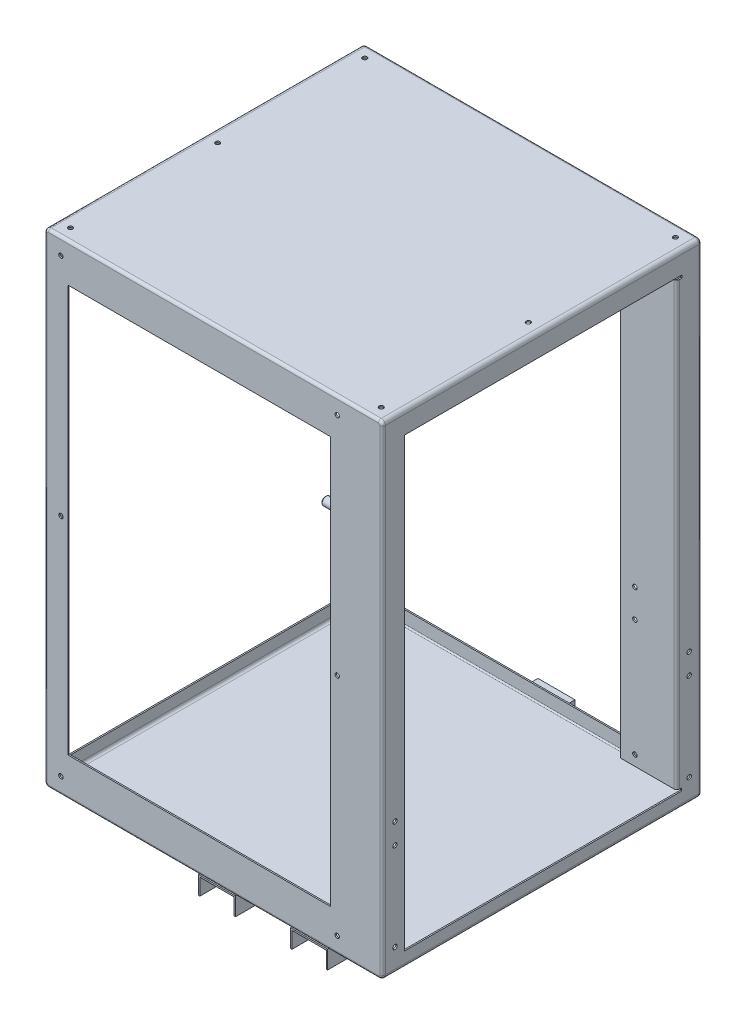
SolidWorks part; units mm, degrees
ref_plane "Спереди" through (0, 0, 0) normal (0, 0, 1) x (1, 0, 0)
ref_plane "Сверху" through (0, 0, 0) normal (0, 1, 0) x (1, 0, 0)
ref_plane "Справа" through (0, 0, 0) normal (1, 0, 0) x (0, 0, -1)
sketch "Эскиз1" plane through (0, 0, 0) normal (0, 0, 1) x (1, 0, 0)
  line L0 (-33.8044, 0) -> (37.3961, 0) construction
  line L1 (0, -31.1634) -> (0, 34.1213) construction
  line L3 (-120, -175) -> (120, -175)
  line L4 (-122, -173) -> (-122, 173)
  line L5 (-120, 175) -> (120, 175)
  line L6 (122, -173) -> (122, 173)
  arc A0 (-122, 173) -> (-120, 175) centre (-120, 173) cw
  arc A1 (120, 175) -> (122, 173) centre (120, 173) cw
  arc A2 (-120, -175) -> (-122, -173) centre (-120, -173) cw
  arc A3 (120, -175) -> (122, -173) centre (120, -173) ccw
  point P11 (-122, 175)
  point P14 (122, 175)
  point P17 (-122, -175)
  dimension "D3" = 2
  dimension "D1" = 350
  dimension "D2" = 244
extrude "Вытянуть-Тонкостенный1" add sketch "Эскиз1" along normal blind 232 thin thin type one direction wall 1
sketch "Эскиз2" plane through (123, 0, 0) normal (1, 0, 0) x (0, 0, -1)
  line L0 (-232, 176) -> (0, 176) construction
  line L1 (-216, -165) -> (-16, -165)
  line L2 (-216, -165) -> (-216, 160)
  line L3 (-216, 160) -> (-16, 160)
  line L4 (-16, -165) -> (-16, 160)
  line L5 (-116, 208.5566) -> (-116, -206.9252) construction
  line L6 (-232, -173) -> (-232, 173) construction
  line L7 (0, -173) -> (0, 173) construction
  dimension "D1" = 200
  dimension "D2" = 325
  dimension "D3" = 16
extrude "Вырез-Вытянуть1" cut sketch "Эскиз2" against normal blind 500
sketch "Эскиз3" plane through (0, 0, 232) normal (0, 0, 1) x (1, 0, 0)
  line L4 (-123, 173) -> (-123, -173)
  line L5 (-120, -176) -> (120, -176)
  line L6 (123, -173) -> (123, 173)
  line L7 (120, 176) -> (-120, 176)
  line L8 (-123, 173) -> (-123, -173)
  line L9 (-120, -176) -> (120, -176)
  line L10 (123, -173) -> (123, 173)
  line L11 (120, 176) -> (-120, 176)
  arc A4 (-120, 176) -> (-123, 173) centre (-120, 173) ccw
  arc A5 (-123, -173) -> (-120, -176) centre (-120, -173) ccw
  arc A6 (120, -176) -> (123, -173) centre (120, -173) ccw
  arc A7 (123, 173) -> (120, 176) centre (120, 173) ccw
  arc A8 (-120, 176) -> (-123, 173) centre (-120, 173) ccw
  arc A9 (-123, -173) -> (-120, -176) centre (-120, -173) ccw
  arc A10 (120, -176) -> (123, -173) centre (120, -173) ccw
  arc A11 (123, 173) -> (120, 176) centre (120, 173) ccw
  dimension "D1" = 0
extrude "Вытянуть1" add sketch "Эскиз3" against normal blind 1
sketch "Эскиз4" plane through (0, 0, 0) normal (0, 0, -1) x (-1, 0, 0)
  line L1 (0, 0) -> (0, 114.475) construction
  line L3 (-107, -165) -> (107, -165)
  line L4 (120, 176) -> (-120, 176)
  line L5 (-123, 173) -> (-123, -173)
  line L6 (-120, -176) -> (120, -176)
  line L7 (123, -173) -> (123, 173)
  line L8 (120, 176) -> (-120, 176)
  line L9 (-123, 173) -> (-123, -173)
  line L10 (-120, -176) -> (120, -176)
  line L11 (123, -173) -> (123, 173)
  line L12 (-107, -165) -> (-107, 160)
  line L13 (-107, 160) -> (107, 160)
  line L14 (107, -165) -> (107, 160)
  arc A4 (123, 173) -> (120, 176) centre (120, 173) ccw
  arc A5 (-120, 176) -> (-123, 173) centre (-120, 173) ccw
  arc A6 (-123, -173) -> (-120, -176) centre (-120, -173) ccw
  arc A7 (120, -176) -> (123, -173) centre (120, -173) ccw
  arc A8 (123, 173) -> (120, 176) centre (120, 173) ccw
  arc A9 (-120, 176) -> (-123, 173) centre (-120, 173) ccw
  arc A10 (-123, -173) -> (-120, -176) centre (-120, -173) ccw
  arc A11 (120, -176) -> (123, -173) centre (120, -173) ccw
  dimension "D2" = 214
  dimension "D3" = 325
  dimension "D4" = 16
  dimension "D1" = 0
extrude "Вытянуть2" add sketch "Эскиз4" against normal blind 1
fillet "Скругление1" radius 1 16 edges at (121.4142, 174.4142, 231) (122, 0, 231) (121.4142, -174.4142, 231) (0, -175, 231) (-121.4142, -174.4142, 231) (-122, 0, 231) (-121.4142, 174.4142, 231) (-121.4142, 174.4142, 1) (-122, 0, 1) (-121.4142, -174.4142, 1) (0, -175, 1) (121.4142, -174.4142, 1) (122, 0, 1) (121.4142, 174.4142, 1) (0, 175, 231) (0, 175, 1)
fillet "Скругление2" radius 2 16 edges at (-122.1213, 175.1213, 232) (0, 176, 232) (122.1213, 175.1213, 232) (123, 0, 232) (122.1213, -175.1213, 232) (0, -176, 232) (-122.1213, -175.1213, 232) (-122.1213, 175.1213, 0) (0, 176, 0) (122.1213, 175.1213, 0) (123, 0, 0) (122.1213, -175.1213, 0) (0, -176, 0) (-122.1213, -175.1213, 0) (-123, 0, 232) (-123, 0, 0)
sketch "Эскиз6" plane through (-123, 0, 0) normal (-1, 0, 0) x (0, 0, 1)
  line L0 (230, -176) -> (2, -176) construction
  line L1 (16, -165) -> (16, 160) construction
  circle A0 centre (8, -118) radius 3
  dimension "D1" = 6
  dimension "D3" = 8
  dimension "D2" = 58
extrude "Вытянуть3" add sketch "Эскиз6" along normal blind 20
chamfer "Фаска1" distance 1 angle 45 1 edges at (-143, -118, 11)
sketch "Эскиз7" plane through (-123, 0, 0) normal (-1, 0, 0) x (0, 0, 1)
  line L0 (9, -170.4186) -> (9, -81.3043) construction
  line L1 (230, -176) -> (2, -176) construction
  line L2 (0, -173) -> (0, 173) construction
  line L3 (116, 41.2045) -> (116, -219.7788) construction
  line L6 (16, -165) -> (16, 160) construction
  line L7 (216, 160) -> (216, -165) construction
  circle A0 centre (9, -95) radius 1.6
  circle A1 centre (9, -159) radius 1.6
  circle A2 centre (223, -95) radius 1.6
  circle A3 centre (223, -159) radius 1.6
  circle A4 centre (9, -80) radius 1.6
  circle A5 centre (223, -80) radius 1.6
  dimension "D4" = 3.2
  dimension "D1" = 17
  dimension "D2" = 81
  dimension "D3" = 9
  dimension "D5" = 96
extrude "Вырез-Вытянуть3" cut sketch "Эскиз7" against normal blind 500
sketch "Эскиз8" plane through (0, 0, 232) normal (0, 0, 1) x (1, 0, 0)
  line L0 (-123, -173) -> (-123, 173) construction
  line L1 (-106, -148) -> (85, -148)
  line L2 (-106, -148) -> (-106, 148)
  line L3 (-106, 148) -> (85, 148)
  line L4 (85, -148) -> (85, 148)
  line L5 (-120, 176) -> (120, 176) construction
  line L6 (120, -176) -> (-120, -176) construction
  line L7 (123, 173) -> (123, -173) construction
  dimension "D1" = 17
  dimension "D2" = 28
  dimension "D3" = 28
  dimension "D4" = 38
extrude "Вырез-Вытянуть4" cut sketch "Эскиз8" against normal blind 2
sketch "Эскиз9" plane through (0, 0, 232) normal (0, 0, 1) x (1, 0, 0)
  line L0 (-120, 176) -> (120, 176) construction
  line L1 (-123, -173) -> (-123, 173) construction
  line L2 (0, 0) -> (-174.4696, 0) construction
  line L3 (-10.5, 126.3418) -> (-10.5, -63.6186) construction
  line L4 (120, -176) -> (-120, -176) construction
  line L5 (-106, 148) -> (-106, -148) construction
  line L6 (85, -148) -> (85, 148) construction
  circle A0 centre (-111, 164) radius 1.6
  circle A1 centre (-111, 0) radius 1.6
  circle A2 centre (-111, -164) radius 1.6
  circle A3 centre (90, -164) radius 1.6
  circle A4 centre (90, 0) radius 1.6
  circle A5 centre (90, 164) radius 1.6
  dimension "D1" = 12
  dimension "D3" = 3.2
  dimension "D4" = 3.2
  dimension "D2" = 12
  dimension "D5" = 12
extrude "Вырез-Вытянуть5" cut sketch "Эскиз9" against normal blind 2
sketch "Эскиз10" plane through (123, 0, 0) normal (0, 0, 1) x (1, 0, 0)
  line L0 (-134, -176.0152) -> (-134, -175.8152)
  line L1 (-134, -189.0152) -> (-134, -176.0152)
  line L2 (-133, -189.0152) -> (-133, -177.0152)
  line L3 (-133, -177.0152) -> (-108, -177.0152)
  line L4 (-108, -189.0152) -> (-108, -177.0152)
  line L5 (-107, -175.8152) -> (-134, -175.8152)
  line L6 (-67, -176.0152) -> (-67, -175.8152)
  line L7 (-107, -189.0152) -> (-107, -176.0152)
  line L8 (-134, -189.0152) -> (-133, -189.0152)
  line L9 (-108, -189.0152) -> (-107, -189.0152)
  line L10 (-87, -139.0452) -> (-87, -213.9051) construction
  line L11 (-66, -189.0152) -> (-67, -189.0152)
  line L12 (-40, -189.0152) -> (-41, -189.0152)
  line L13 (-67, -189.0152) -> (-67, -176.0152)
  line L14 (-67, -175.8152) -> (-40, -175.8152)
  line L15 (-66, -189.0152) -> (-66, -177.0152)
  line L16 (-41, -177.0152) -> (-66, -177.0152)
  line L17 (-41, -189.0152) -> (-41, -177.0152)
  line L18 (-40, -189.0152) -> (-40, -176.0152)
  line L19 (-40, -176.0152) -> (-40, -175.8152)
  line L20 (0, 173) -> (0, -173) construction
  line L21 (-107, -176.0152) -> (-107, -175.8152)
  line L25 (-134, -176.0152) -> (-107, -176.0152) construction
  dimension "D1" = 40
  dimension "D2" = 12
  dimension "D3" = 25
  dimension "D4" = 12
  dimension "D6" = 20
  dimension "D5" = 1
extrude "Вытянуть6" add sketch "Эскиз10" along normal up to surface (232 mm away) and the other way blind 15 up to face at (88.4, 164, 232)
sketch "Эскиз16" plane through (0, 0, 16) normal (0, 0, 1) x (1, 0, 0)
  line L4 (122, 160) -> (122, -165)
  line L5 (122, -165) -> (123, -165)
  line L6 (123, -165) -> (123, 160)
  line L7 (123, 160) -> (122, 160)
  line L8 (122, 160) -> (122, -165)
  line L9 (122, -165) -> (123, -165)
  line L10 (123, -165) -> (123, 160)
  line L11 (123, 160) -> (122, 160)
  line L12 (-123, -165) -> (-122, -165)
  line L13 (-122, -165) -> (-122, 160)
  line L14 (-122, 160) -> (-123, 160)
  line L15 (-123, 160) -> (-123, -165)
  line L16 (-123, -165) -> (-122, -165)
  line L17 (-122, -165) -> (-122, 160)
  line L18 (-122, 160) -> (-123, 160)
  line L19 (-123, 160) -> (-123, -165)
  dimension "D1" = 0
  dimension "D2" = 0
extrude "Вытянуть9" add sketch "Эскиз16" along normal blind 2
sketch "Эскиз17" plane through (122, 0, 0) normal (-1, 0, 0) x (0, 0, 1)
  line L0 (18, 160) -> (18, -165) construction
  line L1 (18, -165) -> (216, -165) construction
  line L2 (18, -163) -> (17, -163)
  line L3 (18, -163) -> (18, 158)
  line L4 (18, 158) -> (17, 158)
  line L5 (17, -163) -> (17, 158)
  line L6 (216, 160) -> (18, 160) construction
  dimension "D1" = 1
  dimension "D2" = 2
  dimension "D3" = 2
extrude "Вытянуть10" add sketch "Эскиз17" along normal blind 40
sketch "Эскиз18" plane through (-122, 0, 0) normal (1, 0, 0) x (0, 0, -1)
  line L4 (-18, 158) -> (-18, -163)
  line L5 (-17, 158) -> (-18, 158)
  line L6 (-17, -163) -> (-17, 158)
  line L7 (-18, -163) -> (-17, -163)
  line L8 (-18, 158) -> (-18, -163)
  line L9 (-17, 158) -> (-18, 158)
  line L10 (-17, -163) -> (-17, 158)
  line L11 (-18, -163) -> (-17, -163)
  dimension "D1" = 0
extrude "Вытянуть11" add sketch "Эскиз18" along normal blind 40
sketch "Эскиз19" plane through (-122, 0, 0) normal (1, 0, 0) x (0, 0, -1)
  line L1 (-18, -165) -> (-14.5, -165)
  line L2 (-18, -165) -> (-18, -163)
  line L3 (-18, -163) -> (-14.5, -163)
  line L4 (-14.5, -165) -> (-14.5, -163)
  line L5 (-18, 160) -> (-14.5, 160)
  line L6 (-18, 160) -> (-18, 158)
  line L7 (-18, 158) -> (-14.5, 158)
  line L8 (-14.5, 160) -> (-14.5, 158)
  dimension "D1" = 3.5
  dimension "D2" = 2
  dimension "D3" = 2
  dimension "D4" = 3.5
extrude "Вырез-Вытянуть8" cut sketch "Эскиз19" against normal blind 40
sketch "Эскиз20" plane through (0, 0, 17) normal (0, 0, -1) x (-1, 0, 0)
  line L0 (0, 0) -> (0, 229.3247) construction
  line L1 (-92.5, 145.5) -> (-92.5, -135.839) construction
  line L2 (-120, 176) -> (120, 176) construction
  circle A0 centre (-92.5, 145.5) radius 1.6
  circle A1 centre (-92.5, -50) radius 1.6
  circle A2 centre (-92.5, -155.5) radius 1.6
  circle A3 centre (92.5, -155.5) radius 1.6
  circle A4 centre (92.5, -50) radius 1.6
  circle A5 centre (92.5, 145.5) radius 1.6
  circle A6 centre (-92.5, -70.5) radius 1.6
  circle A7 centre (92.5, -70.5) radius 1.6
  dimension "D1" = 301
  dimension "D3" = 30.5
  dimension "D4" = 3.2
  dimension "D5" = 195.5
  dimension "D6" = 85
  dimension "D2" = 92.5
extrude "Вырез-Вытянуть9" cut sketch "Эскиз20" against normal blind 10
fillet "Скругление4" radius 2 4 edges at (122, -2.5, 216) (123, -2.5, 18) (-123, -2.5, 18) (-122, -2.5, 216)
sketch "Эскиз22" plane through (122, 0, 0) normal (-1, 0, 0) x (0, 0, 1)
  line L1 (14.5, -165) -> (19.251, -165)
  line L2 (14.5, -165) -> (14.5, -162.9892)
  line L3 (14.5, -162.9892) -> (19.251, -162.9892)
  line L4 (19.251, -165) -> (19.251, -162.9892)
  line L5 (17.7321, 160) -> (14.2321, 160)
  line L6 (17.7321, 160) -> (17.7321, 158)
  line L7 (17.7321, 158) -> (14.2321, 158)
  line L8 (14.2321, 160) -> (14.2321, 158)
  dimension "D1" = 2
  dimension "D2" = 3.5
extrude "Вырез-Вытянуть11" cut sketch "Эскиз22" against normal blind 10
sketch "Эскиз23" plane through (0, 176, 0) normal (0, 1, 0) x (1, 0, 0)
  line L0 (-123, -230) -> (-123, -2) construction
  line L1 (120, -232) -> (-120, -232) construction
  line L2 (-113, -223) -> (-113, -67.0841) construction
  line L3 (0, 0) -> (0, -260.3365) construction
  line L4 (123, -230) -> (123, -2) construction
  circle A0 centre (-113, -223) radius 1.6
  circle A1 centre (-113, -116) radius 1.6
  circle A2 centre (-113, -9) radius 1.6
  circle A3 centre (113, -223) radius 1.6
  circle A4 centre (113, -116) radius 1.6
  circle A5 centre (113, -9) radius 1.6
  dimension "D3" = 3.2
  dimension "D4" = 214
  dimension "D5" = 107
  dimension "D1" = 10
  dimension "D2" = 9
extrude "Вырез-Вытянуть12" cut sketch "Эскиз23" against normal blind 10
